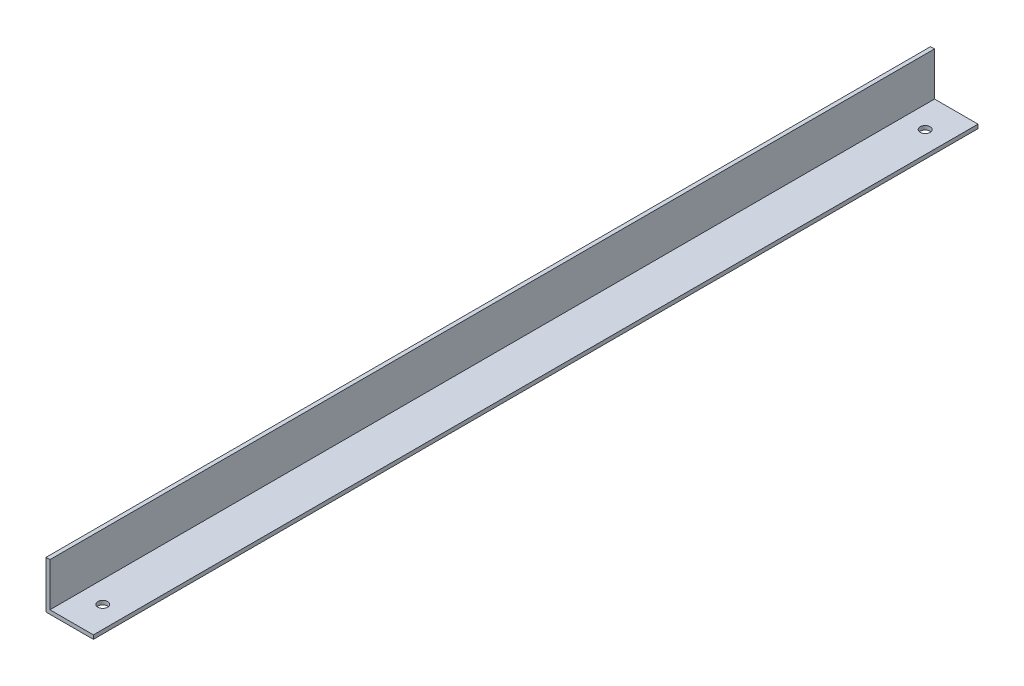
SolidWorks part; units mm, degrees
ref_plane "Front Plane" through (0, 0, 0) normal (0, 0, 1) x (1, 0, 0)
ref_plane "Top Plane" through (0, 0, 0) normal (0, 1, 0) x (1, 0, 0)
ref_plane "Right Plane" through (0, 0, 0) normal (1, 0, 0) x (0, 0, -1)
sketch "Sketch2" plane through (0, 0, 0) normal (0, 0, 1) x (1, 0, 0)
  line L0 (0, -9.525) -> (0, 9.525)
  line L1 (0, 9.525) -> (1.5875, 9.525)
  line L2 (1.5875, 9.525) -> (1.5875, -7.9375)
  line L3 (1.5875, -7.9375) -> (19.05, -7.9375)
  line L4 (19.05, -7.9375) -> (19.05, -9.525)
  line L5 (19.05, -9.525) -> (0, -9.525)
  point P4 (0, 0)
  dimension "D1" = 1.5875
  dimension "D2" = 1.5875
  dimension "D3" = 19.05
  dimension "D4" = 19.05
extrude "Boss-Extrude1" add sketch "Sketch2" along normal blind 355.6
sketch "Sketch3" plane through (0, -7.9375, 0) normal (0, 1, 0) x (1, 0, 0)
  line L0 (10.3188, -355.6) -> (10.3188, 0) construction
  line L1 (19.05, -355.6) -> (1.5875, -355.6) construction
  line L2 (19.05, 0) -> (1.5875, 0) construction
  line L3 (10.3188, -12.5) -> (19.05, -12.5) construction
  line L4 (19.05, -355.6) -> (19.05, 0) construction
  line L5 (19.05, -12.5) -> (19.05, 0) construction
  line L6 (10.3188, -343.1) -> (19.05, -343.1) construction
  line L7 (19.05, -343.1) -> (19.05, -355.6) construction
  circle A0 centre (10.3188, -12.5) radius 1.9844
  circle A1 centre (10.3188, -343.1) radius 1.9844
  dimension "D2" = 3.9688
  dimension "D1" = 12.5
extrude "Cut-Extrude1" cut sketch "Sketch3" against normal up to surface (1.5875 mm away) up to face at (9.525, -9.525, 177.8)
